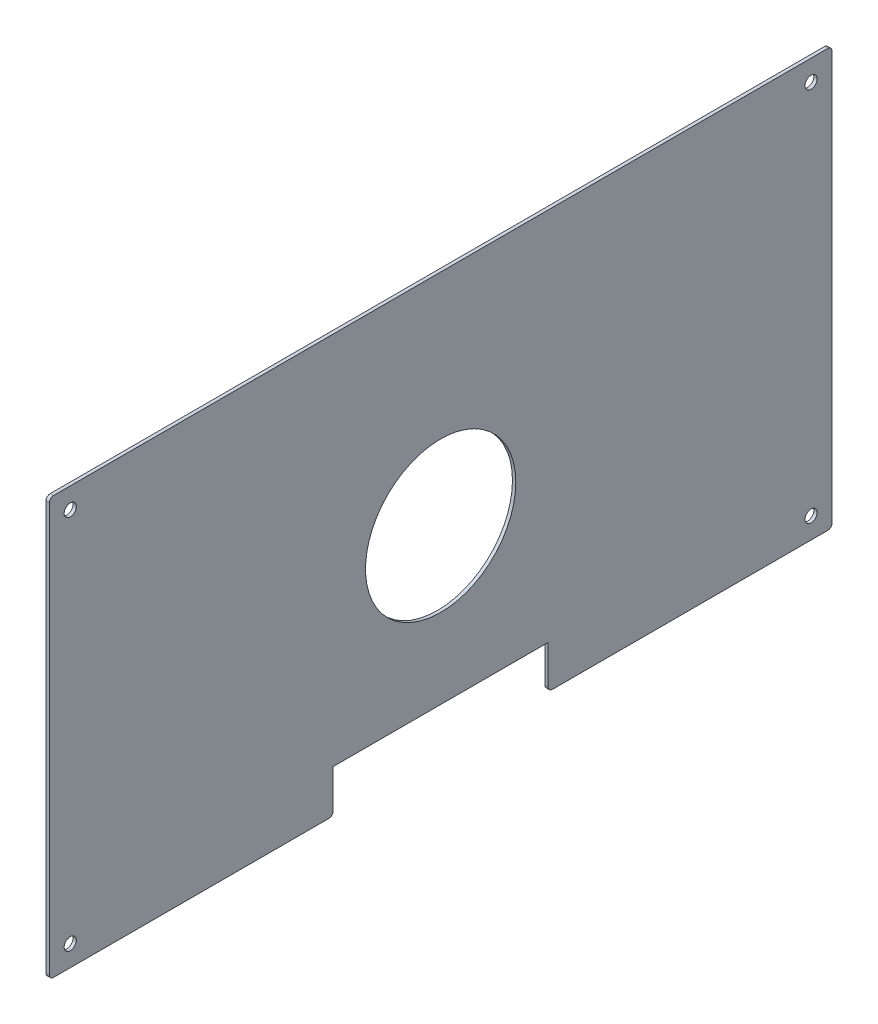
SolidWorks part; units mm, degrees
material "6061 Alloy"
ref_plane "Front Plane" through (0, 0, 0) normal (0, 0, 1) x (1, 0, 0)
ref_plane "Top Plane" through (0, 0, 0) normal (0, 1, 0) x (1, 0, 0)
ref_plane "Right Plane" through (0, 0, 0) normal (1, 0, 0) x (0, 0, -1)
sketch "Sketch1" plane through (0, 0, 0) normal (1, 0, 0) x (0, 0, -1)
  line L0 (0, 55) -> (0, -55) construction
  line L1 (-187.5, -100) -> (187.5, -100)
  line L2 (-187.5, -100) -> (-187.5, 100)
  line L3 (-187.5, 100) -> (187.5, 100)
  line L4 (187.5, -100) -> (187.5, 100)
  line L5 (-187.5, -100) -> (187.5, 100) construction
  line L6 (-187.5, 100) -> (187.5, -100) construction
  line L7 (55, 0) -> (-55, 0) construction
  circle A0 centre (0, 0) radius 20
  point P0 (0, 0)
  point P6 (-172.5, 92.51)
  point P9 (172.5, 92.51)
  point P12 (-172.5, -92.51)
  point P13 (172.5, -92.51)
  dimension "D5" = 40
  dimension "D1" = 375
  dimension "D2" = 200
  dimension "D3" = 7.49
  dimension "D4" = 15
base flange "Base-Flange1" sketch "Sketch1" thickness 1.5875 reverse thickness direction no parameters "D1"=0.7366
hole_wizard "M5 Clearance Hole1" positions "Sketch6" profile "Sketch8" hole size "M5" standard "ANSI Metric" end condition up to next
sketch "Sketch6" plane through (-1.5875, 0, 0) normal (-1, 0, 0) x (0, 0, 1)
  line L0 (-187.5, 100) -> (187.5, 100) construction
  line L1 (187.5, 100) -> (187.5, -100) construction
  point P0 (177.5, 90)
  dimension "D1" = 10
  dimension "D2" = 10
sketch "Sketch8" plane through (-1.5875, 90, 177.5) normal (0, 1, 0) x (0, 0, 1)
  line L0 (0, 0) -> (0, 1.5875)
  line L1 (0, 1.5875) -> (2.9, 1.5875)
  line L2 (2.9, 1.5875) -> (2.9, 0)
  line L5 (2.9, 0) -> (0, 0)
  line L11 (0, -6.35) -> (0, 107.95) construction
  dimension "Thru Hole Dia." = 5.8
  dimension "Thru Hole Depth" = 1.5875
mirror "Mirror1" about plane through (0, 0, 0) normal (0, 0, 1) of "M5 Clearance Hole1"
mirror "Mirror2" about plane through (0, 0, 0) normal (0, 1, 0) of "Mirror1", "M5 Clearance Hole1"
fillet "Fillet1" radius 2 1 edges at (-0.7937, -100, -187.5)
fillet "Fillet2" radius 2 1 edges at (-0.7937, 100, -187.5)
fillet "Fillet3" radius 2 1 edges at (-0.7937, 100, 187.5)
fillet "Fillet4" radius 2 1 edges at (-0.7937, -100, 187.5)
sketch "Sketch9" plane through (0, 0, 0) normal (1, 0, 0) x (0, 0, -1)
  line L0 (51.5, -100) -> (51.5, -79.5)
  line L1 (-185.5, -100) -> (185.5, -100) construction
  line L2 (51.5, -79.5) -> (-51.5, -79.5)
  line L3 (-51.5, -79.5) -> (-51.5, -100)
  line L4 (-51.5, -100) -> (51.5, -100)
  point P4 (0, -100)
  dimension "D1" = 103
  dimension "D2" = 20.5
extrude "Cut-Extrude1" cut sketch "Sketch9" against normal blind 10 contours L4 L0 L2 L3 normal cut yes
fillet "Fillet5" radius 2 1 edges at (-0.7938, -100, -51.5)
fillet "Fillet6" radius 2 1 edges at (-0.7938, -100, 51.5)
sketch "Sketch10" plane through (0, 0, 0) normal (1, 0, 0) x (0, 0, -1)
  circle A0 centre (0, 0) radius 20
extrude "Boss-Extrude1" add sketch "Sketch10" against normal up to surface (1.5875 mm away) up to face at (-1.5875, -39.702, 0)
sketch "Sketch11" plane through (0, 0, 0) normal (1, 0, 0) x (0, 0, -1)
  circle A0 centre (0, -5.28) radius 36
  dimension "D1" = 72
  dimension "D2" = 5.28
extrude "Cut-Extrude2" cut sketch "Sketch11" against normal blind 10 normal cut yes
sketch "Lignes de pliage1" [suppressed] plane through (0, 0, 0) normal (0, 1, 0) x (1, 0, 0)
sketch "Cube de visualisation1" [suppressed] plane through (0, 0, 0) normal (0, 1, 0) x (1, 0, 0)
sheet metal parameters "Tôlerie1" thickness 1.5875 parameters "D1"=0.7366
flat pattern "Etat déplié1" [suppressed]
sketch "Lignes de pliage2" plane through (0, 0, 0) normal (0, 1, 0) x (1, 0, 0)
sketch3d "Cube de visualisation2" [suppressed]
  line L0 (-187.5, -72.49, 0) -> (187.5, -72.49, 0) construction
  line L1 (-187.5, 72.49, 0) -> (187.5, 72.49, 0) construction
  line L2 (-187.5, -72.49, 0) -> (-187.5, 72.49, 0) construction
  line L3 (187.5, -72.49, 0) -> (187.5, 72.49, 0) construction
sheet metal parameters "Tôlerie2" thickness 1.5875 parameters "D1"=0.7366
flat pattern "Etat déplié1"
sketch "Lignes de pliage2" plane through (0, 0, 0) normal (0, 1, 0) x (1, 0, 0)
sketch3d "Cube de visualisation2" [suppressed]
  line L0 (187.5, -72.49, 0) -> (-187.5, -72.49, 0) construction
  line L1 (187.5, 72.49, 0) -> (-187.5, 72.49, 0) construction
  line L2 (187.5, -72.49, 0) -> (187.5, 72.49, 0) construction
  line L3 (-187.5, -72.49, 0) -> (-187.5, 72.49, 0) construction
sheet metal parameters "Tôlerie3" thickness 1.5875 parameters "D1"=0.7366
flat pattern "Etat déplié1"
sketch "Lignes de pliage2" plane through (0, 0, 0) normal (0, 1, 0) x (1, 0, 0)
sketch3d "Cube de visualisation2" [suppressed]
  line L0 (187.5, -72.49, 0) -> (-187.5, -72.49, 0) construction
  line L1 (187.5, 72.49, 0) -> (-187.5, 72.49, 0) construction
  line L2 (187.5, -72.49, 0) -> (187.5, 72.49, 0) construction
  line L3 (-187.5, -72.49, 0) -> (-187.5, 72.49, 0) construction
sheet metal parameters "Tôlerie4" thickness 1.5875 parameters "D1"=0.7366
flat pattern "Etat déplié1"
sketch "Lignes de pliage2" plane through (0, 0, 0) normal (0, 1, 0) x (1, 0, 0)
sketch3d "Cube de visualisation2" [suppressed]
  line L0 (187.5, -100, 0) -> (-187.5, -100, 0) construction
  line L1 (187.5, 100, 0) -> (-187.5, 100, 0) construction
  line L2 (187.5, -100, 0) -> (187.5, 100, 0) construction
  line L3 (-187.5, -100, 0) -> (-187.5, 100, 0) construction
sheet metal parameters "Tôlerie7" thickness 1.5875 parameters "D1"=0.7366
flat pattern "Etat déplié1"
sketch "Lignes de pliage2" plane through (0, 0, 0) normal (0, 1, 0) x (1, 0, 0)
sketch3d "Cube de visualisation2" [suppressed]
  line L0 (187.5, -100, 0) -> (-187.5, -100, 0) construction
  line L1 (187.5, 100, 0) -> (-187.5, 100, 0) construction
  line L2 (187.5, -100, 0) -> (187.5, 100, 0) construction
  line L3 (-187.5, -100, 0) -> (-187.5, 100, 0) construction
sheet metal parameters "Sheet-Metal8" thickness 1.5875 parameters "D1"=0.7366
flat pattern "Etat déplié1"
sketch "Lignes de pliage2" plane through (0, 0, 0) normal (0, 1, 0) x (1, 0, 0)
sketch3d "Cube de visualisation2" [suppressed]
  line L0 (187.5, -100, 0) -> (-187.5, -100, 0) construction
  line L1 (187.5, 100, 0) -> (-187.5, 100, 0) construction
  line L2 (187.5, -100, 0) -> (187.5, 100, 0) construction
  line L3 (-187.5, -100, 0) -> (-187.5, 100, 0) construction
sheet metal parameters "Sheet-Metal9" thickness 1.5875 parameters "D1"=0.7366
flat pattern "Etat déplié1"
sketch "Lignes de pliage2" plane through (0, 0, 0) normal (0, 1, 0) x (1, 0, 0)
sketch3d "Cube de visualisation2" [suppressed]
  line L0 (187.5, -100, 0) -> (-187.5, -100, 0) construction
  line L1 (187.5, 100, 0) -> (-187.5, 100, 0) construction
  line L2 (187.5, -100, 0) -> (187.5, 100, 0) construction
  line L3 (-187.5, -100, 0) -> (-187.5, 100, 0) construction
